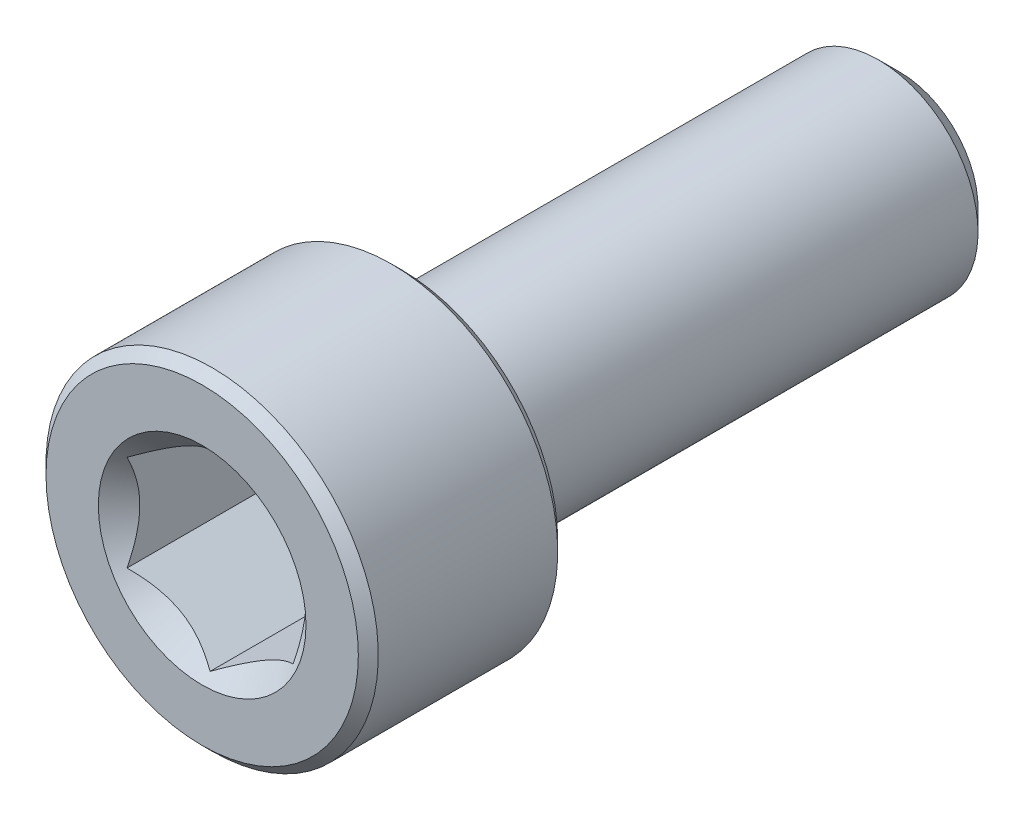
SolidWorks part; units mm, degrees
ref_plane "Front Plane" through (0, 0, 0) normal (0, 0, 1) x (1, 0, 0)
ref_plane "Top Plane" through (0, 0, 0) normal (0, 1, 0) x (1, 0, 0)
ref_plane "Right Plane" through (0, 0, 0) normal (1, 0, 0) x (0, 0, -1)
sketch "Sketch1" plane through (0, 0, 0) normal (1, 0, 0) x (0, 0, -1)
  line L0 (-10.5, 0) -> (10.5, 0) construction
  line L1 (10.5, 0) -> (10.5, 2.3505) construction
  line L2 (10.5, 2.3505) -> (9.8505, 3) construction
  line L3 (9.8505, 3) -> (9.75, 3) construction
  line L4 (9.75, 3) -> (-4.5, 3) construction
  line L5 (-4.5, 3) -> (-4.5, 5) construction
  line L6 (-4.5, 5) -> (-10.5, 5) construction
  line L7 (-10.5, 5) -> (-10.5, 0) construction
  line L8 (10.5, 2.3505) -> (10.5, 3) construction
  line L9 (10.4375, 3.1083) -> (10.9375, 2.2422) construction
  line L10 (10.9375, 2.2422) -> (11.4375, 3.1083) construction
  line L11 (11.4375, 3.1083) -> (10.4375, 3.1083) construction
  line L12 (10.9375, 3.1083) -> (10.9375, 3) construction
  line L13 (10.9375, 2.2422) -> (10.9375, 2.3505) construction
  line L14 (10.875, 2.3505) -> (11, 2.3505) construction
  line L15 (10.5, 3) -> (11.375, 3) construction
  line L16 (10.4687, 3.0541) -> (11.4062, 3.0541) construction
  line L17 (10.5, 0) -> (10.5, -3) construction
  line L18 (-4.8, 5) -> (-4.5, 4.7) construction
  line L19 (-10.2, 5) -> (-10.5, 4.7) construction
  line L20 (-4.5, 3) -> (-4.5, 0) construction
  line L21 (-4.5, 1.5) -> (0.5, 1.5) construction
  line L22 (0.5, 1.5) -> (5.5, 1.5) construction
  line L23 (5.5, 1.5) -> (10.5, 1.5) construction
  line L24 (0.5, 1.5) -> (0.5, 3) construction
  line L25 (0.5, 3) -> (0.5, 5) construction
  line L26 (5.5, 1.5) -> (5.5, 5) construction
  point P0 (-10.5, 2.5)
  point P3 (8, 3)
  point P4 (0, 0)
  point P18 (5.5, 3)
  point P22 (10.9375, 2.3505)
  point P24 (9.75, 3)
  point P25 (10.9375, 3)
  point P28 (10.9375, 3.0541)
  point P29 (8, -3)
  point P30 (0.5, 3)
  point P31 (-7.5, 5)
  point P37 (-5.55, 5)
  point P38 (-10.05, 5)
  point P45 (0.5, 1.5)
  point P46 (5.5, 1.5)
  dimension "D2" = 0.125
  dimension "D7" = 0.3
  dimension "D8" = 0.3
  dimension "D9" = 0.3
  dimension "D10" = 0.15
  dimension "D11" = 0.75
  dimension "Drive Size" = 5
  dimension "Head Diameter" = 10
  dimension "Head Height" = 6
  dimension "Thread Pitch" = 1
  dimension "Thread Size" = 6
  dimension "Length" = 15
  dimension "D12" = 0.75
  dimension "D4" = 2.5
  dimension "D3" = 45
sketch "Sketch2" plane through (0, 0, 0) normal (1, 0, 0) x (0, 0, -1)
  line L0 (-10.5, 0) -> (-10.5, 4.7)
  line L1 (-10.2, 5) -> (-4.8, 5)
  line L2 (-4.5, 4.7) -> (-4.5, 3.3)
  line L4 (9.8505, 3) -> (10.5, 2.3505)
  line L5 (10.5, 2.3505) -> (10.5, 0)
  line L6 (-4.5, 5) -> (-10.5, 5) construction
  line L7 (10.5, 0) -> (-10.5, 0)
  line L8 (-10.2, 5) -> (-10.5, 4.7) construction
  line L10 (-10.2, 5) -> (-10.5, 4.7)
  line L14 (-4.8, 5) -> (-4.5, 4.7) construction
  line L16 (-4.8, 5) -> (-4.5, 4.7)
  line L17 (-4.5, 3) -> (-4.5, 5) construction
  line L19 (-4.2, 3) -> (9.8505, 3)
  line L20 (9.75, 3) -> (-4.5, 3) construction
  arc A1 (-4.5, 3.3) -> (-4.2, 3) centre (-4.2, 3.3) ccw
  dimension "D3" = 0.3
revolve "Revolve1" add sketch "Sketch2" angle 360 about L7
sketch "Sketch3" plane through (0, 0, 10.5) normal (0, 0, 1) x (1, 0, 0)
  line L1 (2.5, -1.4434) -> (2.5, 1.4434)
  line L2 (2.5, 1.4434) -> (0, 2.8868)
  line L3 (0, 2.8868) -> (-2.5, 1.4434)
  line L4 (-2.5, 1.4434) -> (-2.5, -1.4434)
  line L5 (-2.5, -1.4434) -> (0, -2.8868)
  line L6 (0, -2.8868) -> (2.5, -1.4434)
  circle A0 centre (0, 0) radius 2.5 construction
  circle A1 centre (0, 0) radius 5 construction
  circle A2 centre (0, 0) radius 5 construction
  circle A3 centre (0, 0) radius 2.8868 construction
  point P13 (0, 0)
extrude "Cut-Extrude1" cut sketch "Sketch3" against normal offset from surface (5 mm away) 1 up to face at (0, 4.7, 4.5)
sketch "Sketch4" plane through (0, 0, 10.5) normal (0, 0, 1) x (1, 0, 0)
  circle A0 centre (0, 0) radius 3.125
  dimension "D1" = 6.25
extrude "Cut-Extrude2" cut sketch "Sketch4" against normal up to vertex (3 mm away) draft 45 up to point (0, 5, 7.5)
sketch "Sketch11" plane through (0, 0, 0) normal (1, 0, 0) x (0, 0, -1)
  line L0 (-10.5, 0) -> (10.5, 0) construction
  line L1 (-10.5, 0) -> (10.5, 0) construction
  line L2 (-1.6875, 0) -> (-1.6875, 3) construction
  line L3 (9.75, 3) -> (-4.5, 3) construction
  line L4 (7.6875, 0) -> (7.6875, 3) construction
  line L6 (10.5, 2.3505) -> (10.5, 3) construction
  point P2 (-1.6875, 0)
  point P3 (7.6875, 0)
  dimension "D1" = 2.8125
  dimension "D2" = 2.8125
equation "\"D2@Sketch1\" = \"Thread Pitch@Sketch1\" / 8"
equation "\"D7@Sketch1\" = \"Head Height@Sketch1\" * .05"
equation "\"D8@Sketch1\"=\"D7@Sketch1\""
equation "\"D9@Sketch1\"=\"D7@Sketch1\""
equation "\"D10@Sketch1\"=\"D7@Sketch1\"/2"
equation "\"D11@Sketch1\"=\"D10@Sketch1\"*5"
equation "\"D4@Sketch1\"=\"Thread Pitch@Sketch1\"*2.5"
equation "\"D12@Sketch1\"=\"Thread Pitch@Sketch1\"*.75"
equation "\"D3@Sketch2\" = \"Thread Size@Sketch1\" * 0.05"
equation "\"D1@Sketch11\"=\"Length@Sketch1\"*0.1875"
equation "\"D2@Sketch11\"=\"D1@Sketch11\""
equation "\"D1@Sketch4\"=\"Drive Size@Sketch1\"*1.25"
